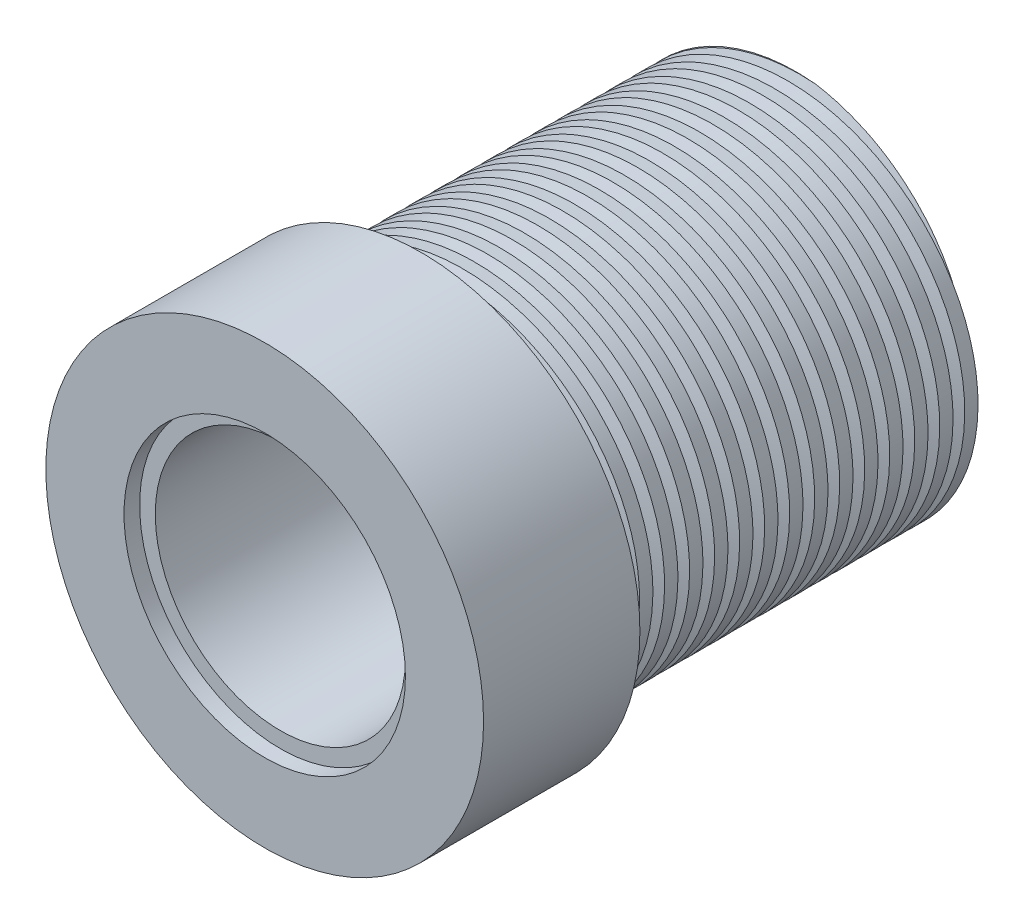
SolidWorks part; units mm, degrees
ref_plane "Front Plane" through (0, 0, 0) normal (0, 0, 1) x (1, 0, 0)
ref_plane "Top Plane" through (0, 0, 0) normal (0, 1, 0) x (1, 0, 0)
ref_plane "Right Plane" through (0, 0, 0) normal (1, 0, 0) x (0, 0, -1)
sketch "Sketch1" plane through (0, 0, 0) normal (0, 0, 1) x (1, 0, 0)
  circle A0 centre (0, 0) radius 6
  dimension "D1" = 12
extrude "Boss-Extrude1" add sketch "Sketch1" along normal blind 12
sketch "Sketch2" plane through (0, 0, 12) normal (0, 0, 1) x (1, 0, 0)
  circle A0 centre (0, 0) radius 7
  dimension "D1" = 14
extrude "Boss-Extrude2" add sketch "Sketch2" along normal blind 5
sketch "Sketch3" plane through (0, 0, 17) normal (0, 0, 1) x (1, 0, 0)
  circle A0 centre (0, 0) radius 4.5
  dimension "D1" = 9
extrude "Cut-Extrude1" cut sketch "Sketch3" against normal blind 0.5
sketch "Sketch4" plane through (0, 0, 0) normal (0, 1, 0) x (1, 0, 0)
  line L0 (5.5, 0) -> (6.5, 0.375)
  line L1 (6, 0) -> (-6, 0) construction
  line L2 (6.5, 0.375) -> (6.5, -0.375)
  line L3 (6.5, -0.375) -> (5.5, 0)
  dimension "D1" = 1
  dimension "D2" = 0.75
  dimension "D3" = 0.375
  dimension "D4" = 5.5
sketch "Sketch5" plane through (0, 0, 0) normal (0, 0, -1) x (-1, 0, 0)
  circle A0 centre (0, 0) radius 6
curve "Helix/Spiral1" pitch 0.8 height 11.6 radius 6 centre (0, 0, 0) axis (0, 0, 1) start towards (1, 0, 0)
sweep "Cut-Sweep1" cut profiles "Sketch4" path "Helix/Spiral1" align with end faces yes
sketch "Sketch6" plane through (0, 0, 16.5) normal (0, 0, 1) x (1, 0, 0)
  circle A0 centre (0, 0) radius 4
  dimension "D1" = 8
extrude "Cut-Extrude2" cut sketch "Sketch6" against normal blind 17
